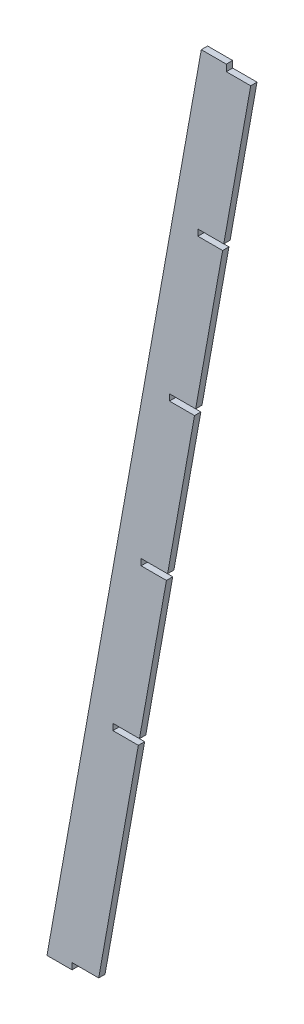
SolidWorks part; units mm, degrees
ref_plane "Front Plane" through (0, 0, 0) normal (0, 0, 1) x (1, 0, 0)
ref_plane "Top Plane" through (0, 0, 0) normal (0, 1, 0) x (1, 0, 0)
ref_plane "Right Plane" through (0, 0, 0) normal (1, 0, 0) x (0, 0, -1)
sketch "Sketch1" plane through (0, 0, 0) normal (0, 1, 0) x (1, 0, 0)
  line L1 (0, 0) -> (25.4, 0)
  line L2 (0, 0) -> (0, 3.175)
  line L3 (0, 3.175) -> (25.4, 3.175)
  line L4 (25.4, 0) -> (25.4, 3.175)
  dimension "D1" = 25.4
  dimension "D2" = 3.175
ref_plane "Plane1" through (0, 432.562, 0) normal (0, 1, 0) x (1, 0, 0)
sketch "Sketch2" plane through (0, 432.562, 0) normal (0, 1, 0) x (1, 0, 0)
  line L1 (77.47, 0) -> (102.87, 0)
  line L2 (77.47, 0) -> (77.47, 3.175)
  line L3 (77.47, 3.175) -> (102.87, 3.175)
  line L4 (102.87, 0) -> (102.87, 3.175)
  dimension "D1" = 25.4
  dimension "D2" = 3.175
  dimension "D3" = 0
  dimension "D4" = 77.47
loft "Loft1" add profiles "Sketch1", "Sketch2" connector at (25.4, 0, 0) connector at (102.87, 432.562, 0)
sketch "Sketch3" plane through (0, 0, 0) normal (0, 0, 1) x (1, 0, 0)
  line L0 (90.0287, 432.562) -> (90.0287, 429.26)
  line L9 (12.5729, 3.175) -> (12.5729, 0)
  line L11 (102.2786, 429.26) -> (90.0287, 429.26)
  line L12 (25.4, 0) -> (102.87, 432.562) construction
  line L13 (90.0287, 432.562) -> (102.87, 432.562)
  line L14 (102.87, 432.562) -> (102.2786, 429.26)
  line L15 (33.0714, 117.475) -> (33.0714, 114.3)
  line L16 (75.7597, 353.7381) -> (75.7597, 350.5952)
  line L17 (75.7597, 353.7381) -> (88.753, 353.7381)
  line L18 (75.7597, 350.5952) -> (88.1901, 350.5952)
  line L19 (88.1901, 350.5952) -> (88.753, 353.7381)
  line L20 (61.4709, 274.955) -> (61.4709, 271.78)
  line L21 (47.2604, 193.04) -> (47.2604, 196.215)
  line L22 (61.4709, 271.78) -> (74.0746, 271.78)
  line L23 (74.0746, 271.78) -> (74.6433, 274.955)
  line L24 (74.6433, 274.955) -> (61.4709, 274.955)
  line L25 (60.5413, 196.215) -> (59.9726, 193.04)
  line L26 (59.9726, 193.04) -> (47.2604, 193.04)
  line L27 (47.2604, 196.215) -> (60.5413, 196.215)
  line L28 (45.8706, 114.3) -> (46.4393, 117.475)
  line L29 (46.4393, 117.475) -> (33.0714, 117.475)
  line L30 (33.0714, 114.3) -> (45.8706, 114.3)
  line L31 (12.5729, 0) -> (25.4, 0)
  line L32 (25.4, 0) -> (25.9686, 3.175)
  line L33 (25.9686, 3.175) -> (12.5729, 3.175)
  point P2 (90.0287, 432.562)
  point P4 (33.0714, 114.3)
  point P11 (47.2604, 196.215)
  point P23 (47.2604, 193.04)
  point P24 (61.4709, 274.955)
  point P25 (61.4709, 271.78)
  point P27 (89.8918, 429.26)
extrude "Cut-Extrude1" cut sketch "Sketch3" against normal blind 5.08
